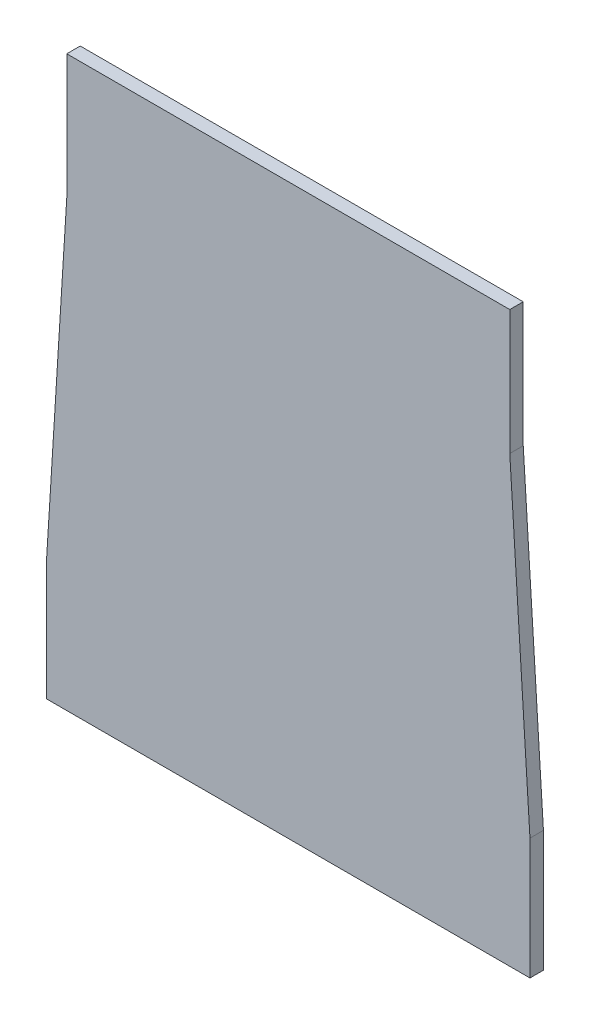
SolidWorks part; units mm, degrees
material "MDF"
ref_plane "Front Plane" through (0, 0, 0) normal (0, 0, 1) x (1, 0, 0)
ref_plane "Top Plane" through (0, 0, 0) normal (0, 1, 0) x (1, 0, 0)
ref_plane "Right Plane" through (0, 0, 0) normal (1, 0, 0) x (0, 0, -1)
sketch "Sketch1" plane through (0, 0, 0) normal (0, 0, 1) x (1, 0, 0)
  line L0 (0, -4273.1683) -> (0, -5592.0408) construction
  line L1 (209.0395, -5469.1795) -> (-209.0395, -5469.1795)
  line L2 (209.0395, -5469.1795) -> (209.0395, -5053.2545)
  line L3 (209.0395, -5053.2545) -> (-209.0395, -5053.2545)
  line L4 (0, -5469.1795) -> (0, -5053.2545) construction
  line L5 (-209.0395, -5469.1795) -> (-209.0395, -5053.2545)
  dimension "D1" = 209.0395
  dimension "D2" = 120.65
  dimension "D3" = 415.925
extrude "Boss-Extrude1" add sketch "Sketch1" along normal blind 12.7
sketch "Sketch2" plane through (0, 0, 0) normal (0, 0, -1) x (-1, 0, 0)
  line L1 (-209.0395, -5469.1795) -> (209.0395, -5469.1795)
  line L2 (-209.0395, -5469.1795) -> (-209.0395, -5577.1295)
  line L3 (-209.0395, -5577.1295) -> (209.0395, -5577.1295)
  line L4 (209.0395, -5469.1795) -> (209.0395, -5577.1295)
  line L8 (209.0395, -5053.2545) -> (209.0395, -5469.1795) construction
  point P7 (0, 0)
  point P8 (0, 0)
  point P11 (0, 0)
  dimension "D1" = 107.95
extrude "Boss-Extrude2" add sketch "Sketch2" against normal through all
sketch "Sketch3" plane through (0, 0, 0) normal (0, 0, -1) x (-1, 0, 0)
  line L1 (209.0395, -5040.3314) -> (-209.0395, -5040.3314)
  line L2 (209.0395, -5040.3314) -> (209.0395, -5053.2545)
  line L3 (209.0395, -5053.2545) -> (-209.0395, -5053.2545)
  line L4 (-209.0395, -5040.3314) -> (-209.0395, -5053.2545)
extrude "Boss-Extrude3" add sketch "Sketch3" against normal through all
sketch "Sketch4" plane through (0, 0, 0) normal (0, 0, -1) x (-1, 0, 0)
  line L0 (209.0388, -5462.8058) -> (228.0888, -5462.8058)
  line L1 (228.0888, -5462.8058) -> (228.0888, -5577.1295)
  line L2 (-209.0395, -5577.1295) -> (209.0395, -5577.1295) construction
  line L3 (228.0888, -5577.1295) -> (209.0395, -5577.1295)
  line L4 (209.0395, -5577.1295) -> (209.0388, -5462.8058)
  line L5 (0, -5578.3233) -> (0, -5040.3314) construction
  line L6 (209.0395, -5040.3314) -> (-209.0395, -5040.3314) construction
  line L7 (-209.0395, -5577.1295) -> (-209.0388, -5462.8058)
  line L8 (-228.0888, -5577.1295) -> (-209.0395, -5577.1295)
  line L9 (-228.0888, -5462.8058) -> (-228.0888, -5577.1295)
  line L10 (-209.0388, -5462.8058) -> (-228.0888, -5462.8058)
extrude "Boss-Extrude4" add sketch "Sketch4" against normal through all
chamfer "Chamfer1" distance 19.05 distance2 304.8 2 edges at (-209.0395, -5462.8058, 6.35) (209.0395, -5462.8058, 6.35) first distance on face at (-218.5641, -5462.8058, 6.35) first distance on face at (218.5641, -5462.8058, 6.35)
